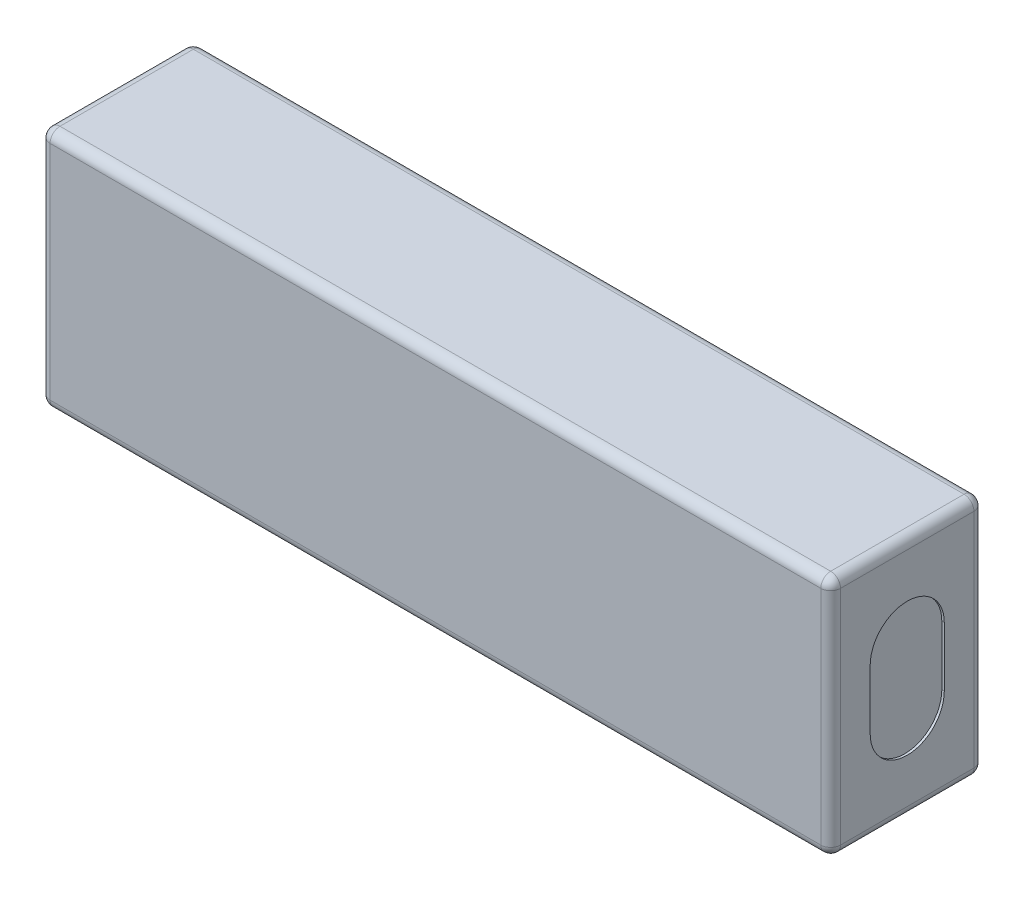
SolidWorks part; units mm, degrees
ref_plane "Plano frontal" through (0, 0, 0) normal (0, 0, 1) x (1, 0, 0)
ref_plane "Plano superior" through (0, 0, 0) normal (0, 1, 0) x (1, 0, 0)
ref_plane "Plano direito" through (0, 0, 0) normal (1, 0, 0) x (0, 0, -1)
sketch "Esboço1" plane through (0, 0, 0) normal (0, 0, 1) x (1, 0, 0)
  line L1 (-80, 24.5) -> (80, 24.5)
  line L2 (-80, 24.5) -> (-80, -24.5)
  line L3 (-80, -24.5) -> (80, -24.5)
  line L4 (80, 24.5) -> (80, -24.5)
  line L5 (-80, 24.5) -> (80, -24.5) construction
  line L6 (-80, -24.5) -> (80, 24.5) construction
  point P0 (0, 0)
  dimension "D1" = 160
  dimension "D2" = 49
extrude "Ressalto-extrusão1" add sketch "Esboço1" along normal mid plane 31
sketch "Esboço2" plane through (80, 0, 0) normal (1, 0, 0) x (0, 0, -1)
  line L0 (0, 24.5) -> (0, -24.5) construction
  line L1 (-15.5, 24.5) -> (15.5, 24.5) construction
  line L2 (-15.5, -24.5) -> (15.5, -24.5) construction
  line L3 (0, 0) -> (-15.5, 0) construction
  line L4 (-15.5, -24.5) -> (-15.5, 24.5) construction
  line L5 (0, 6) -> (0, -6) construction
  line L6 (7.5, 6) -> (7.5, -6)
  line L7 (-7.5, 6) -> (-7.5, -6)
  arc A0 (7.5, 6) -> (-7.5, 6) centre (0, 6) ccw
  arc A1 (-7.5, -6) -> (7.5, -6) centre (0, -6) ccw
  point P13 (0, 0)
  dimension "D1" = 12
  dimension "D2" = 15
extrude "Corte-extrusão1" cut sketch "Esboço2" against normal blind 0.5
mirror "Espelhar1" about plane through (0, 0, 0) normal (1, 0, 0) of "Corte-extrusão1"
fillet "Filete1" radius 2 12 edges at (-80, -24.5, 0) (80, -24.5, 0) (-80, 0, -15.5) (0, -24.5, -15.5) (80, 0, -15.5) (80, 24.5, 0) (-80, 24.5, 0) (0, 24.5, -15.5) (0, -24.5, 15.5) (-80, 0, 15.5) (0, 24.5, 15.5) (80, 0, 15.5)
